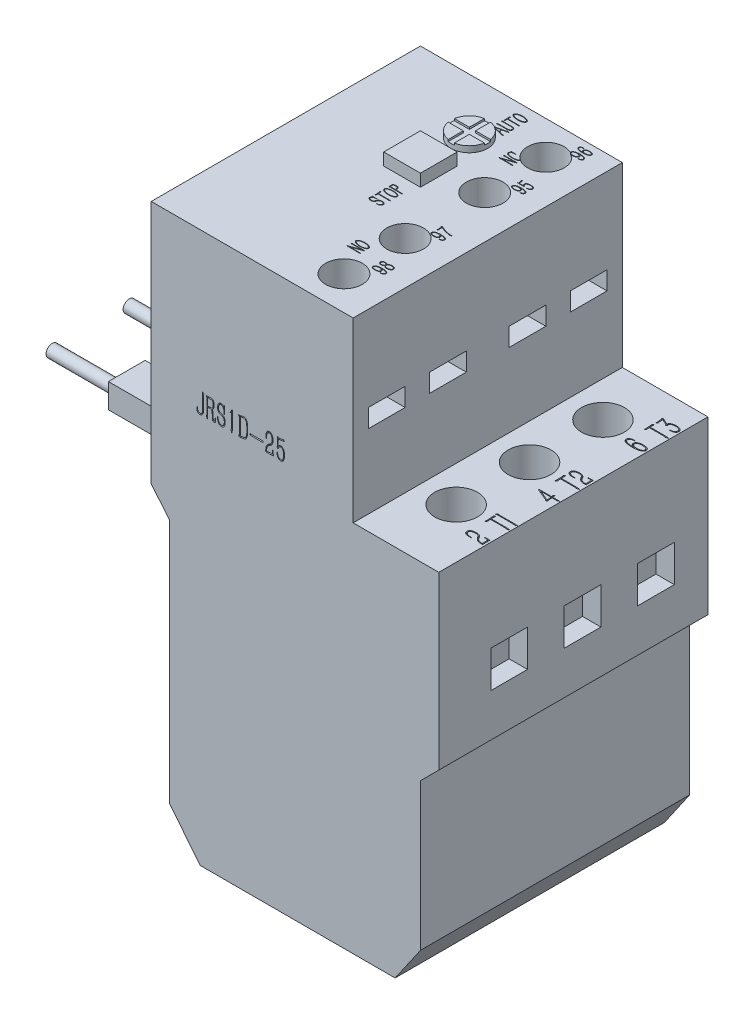
SolidWorks part; units mm, degrees
ref_plane "前视基准面" through (0, 0, 0) normal (0, 0, 1) x (1, 0, 0)
ref_plane "上视基准面" through (0, 0, 0) normal (0, 1, 0) x (1, 0, 0)
ref_plane "右视基准面" through (0, 0, 0) normal (1, 0, 0) x (0, 0, -1)
sketch "草图1" plane through (0, 0, 0) normal (0, 1, 0) x (1, 0, 0)
  line L1 (-23.5, 22) -> (23.5, 22)
  line L2 (-23.5, 22) -> (-23.5, -22)
  line L3 (-23.5, -22) -> (23.5, -22)
  line L4 (23.5, 22) -> (23.5, -22)
  line L5 (-23.5, 22) -> (23.5, -22) construction
  line L6 (-23.5, -22) -> (23.5, 22) construction
  point P0 (0, 0)
  dimension "D1" = 47
  dimension "D2" = 44
extrude "凸台-拉伸1" add sketch "草图1" along normal blind 90
fillet "圆角1" radius 5 1 edges at (23.5, 0, 0)
sketch "草图2" plane through (0, 0, 22) normal (0, 0, 1) x (1, 0, 0)
  line L0 (-23.5, 0) -> (-15.5, 0)
  line L2 (-23.5, 90) -> (-23.5, 0) construction
  line L3 (-23.5, 10) -> (-23.5, 0)
  line L4 (-23.5, 0) -> (18.5, 0) construction
  line L5 (-15.5, 0) -> (-23.5, 10)
  dimension "D1" = 10
  dimension "D2" = 8
extrude "切除-拉伸1" cut sketch "草图2" against normal blind 53
sketch "草图3" plane through (23.5, 0, 0) normal (1, 0, 0) x (0, 0, -1)
sketch "草图5" plane through (0, 0, 22) normal (0, 0, 1) x (1, 0, 0)
  line L0 (23.5, 61) -> (9.5, 61)
  line L1 (23.5, 90) -> (23.5, 5) construction
  line L2 (9.5, 61) -> (9.5, 90)
  line L3 (-23.5, 90) -> (23.5, 90) construction
  line L4 (9.5, 90) -> (23.5, 90)
  line L5 (23.5, 90) -> (23.5, 61)
  line L6 (-15.5, 0) -> (18.5, 0) construction
  dimension "D1" = 14
  dimension "D2" = 61
extrude "切除-拉伸3" cut sketch "草图5" against normal blind 53
sketch "草图6" plane through (-23.5, 0, 0) normal (-1, 0, 0) x (0, 0, 1)
  line L0 (8.4, 60) -> (2.4, 60)
  line L2 (22, 90) -> (22, 10) construction
  line L3 (21, 56) -> (15, 56)
  line L4 (21, 56) -> (21, 60)
  line L5 (21, 60) -> (15, 60)
  line L6 (15, 56) -> (15, 60)
  line L7 (8.4, 56) -> (8.4, 60)
  line L8 (2.4, 56) -> (2.4, 60)
  line L9 (8.4, 56) -> (2.4, 56)
  line L10 (-4.2, 60) -> (-10.2, 60)
  line L11 (-4.2, 56) -> (-4.2, 60)
  line L12 (-10.2, 56) -> (-10.2, 60)
  line L13 (-4.2, 56) -> (-10.2, 56)
  dimension "D2" = 4
  dimension "D1" = 3
  dimension "D3" = 1
  dimension "D4" = 6
extrude "凸台-拉伸2" add sketch "草图6" along normal blind 8
sketch "草图7" plane through (-31.5, 0, 0) normal (-1, 0, 0) x (0, 0, 1)
  circle A0 centre (19.1974, 58) radius 1
  circle A1 centre (6.5974, 58) radius 1
  circle A2 centre (-6.0026, 58) radius 1
  dimension "D1" = 2
  dimension "D2" = 3
extrude "凸台-拉伸3" add sketch "草图7" along normal blind 11
sketch "草图8" plane through (0, 0, 22) normal (0, 0, 1) x (1, 0, 0)
  line L0 (-23.5, 50) -> (-20.5, 46.3906)
  line L1 (-23.5, 90) -> (-23.5, 10) construction
  line L2 (-20.5, 46.3906) -> (-20.5, 5.4883)
  line L4 (-23.5, 50) -> (-23.5, 10)
  line L5 (-23.5, 10) -> (-20.5, 5.4883)
  dimension "D1" = 3
extrude "切除-拉伸4" cut sketch "草图8" against normal blind 64
sketch "草图9" plane through (0, 61, 0) normal (0, 1, 0) x (1, 0, 0)
  line L0 (23.5, 22) -> (18.5, 22) construction
  line L1 (9.5, 22) -> (23.5, 22) construction
  circle A0 centre (15.3377, 13) radius 3.5
  dimension "D1" = 7
  dimension "D2" = 9
extrude "切除-拉伸5" cut sketch "草图9" against normal blind 15
pattern_linear "阵列(线性)1" count 3 spacing 12 along (0, 0, 1) of "切除-拉伸5"
sketch "草图11" plane through (23.5, 0, 0) normal (1, 0, 0) x (0, 0, -1)
  line L0 (22, 61) -> (22, 5) construction
  line L1 (16.5, 46) -> (10.5, 46)
  line L2 (16.5, 46) -> (16.5, 40)
  line L3 (16.5, 40) -> (10.5, 40)
  line L4 (10.5, 46) -> (10.5, 40)
  line L5 (22, 61) -> (-22, 61) construction
  dimension "D1" = 5.5
  dimension "D2" = 15
  dimension "D3" = 6
  dimension "D4" = 6
extrude "切除-拉伸7" cut sketch "草图11" against normal blind 3
pattern_linear "阵列(线性)2" count 3 spacing 12 along (0, 0, 1) of "切除-拉伸7"
sketch "草图12" plane through (0, 0, 22) normal (0, 0, 1) x (1, 0, 0)
  line L0 (23.5, 33) -> (20.5186, 30.0186)
  line L1 (23.5, 61) -> (23.5, 5) construction
  line L2 (20.5186, 30.0186) -> (20.5186, 6.0037)
  line L3 (20.5186, 6.0037) -> (16.3593, 0)
  line L4 (-15.5, 0) -> (18.5, 0) construction
  line L5 (16.3593, 0) -> (23.5, 0)
  line L6 (23.5, 0) -> (23.5, 33)
extrude "切除-拉伸8" cut sketch "草图12" against normal blind 61
sketch "草图13" plane through (0, 90, 0) normal (0, 1, 0) x (1, 0, 0)
  line L0 (9.5, 22) -> (-23.5, 22) construction
  line L1 (9.5, 22) -> (9.5, -22) construction
  circle A0 centre (2.5, 16.5) radius 3
  dimension "D1" = 6
  dimension "D2" = 5.5
  dimension "D3" = 7
extrude "切除-拉伸9" cut sketch "草图13" against normal blind 10
pattern_linear "阵列(线性)3" count 2 spacing 10 along (0, 0, 1) of "切除-拉伸9"
mirror "镜向1" about plane through (0, 0, 0) normal (0, 0, 1) of "阵列(线性)3"
sketch "草图14" plane through (9.5, 0, 0) normal (1, 0, 0) x (0, 0, -1)
  line L0 (22, 90) -> (22, 61) construction
  line L1 (19.5, 73.0813) -> (13.5, 73.0813)
  line L2 (19.5, 73.0813) -> (19.5, 76.0813)
  line L3 (19.5, 76.0813) -> (13.5, 76.0813)
  line L4 (13.5, 73.0813) -> (13.5, 76.0813)
  dimension "D1" = 6
  dimension "D2" = 2.5
  dimension "D3" = 3
extrude "切除-拉伸10" cut sketch "草图14" against normal blind 3
pattern_linear "阵列(线性)4" count 2 spacing 10 along (0, 0, 1) of "切除-拉伸10"
mirror "镜向2" about plane through (0, 0, 0) normal (0, 0, 1) of "阵列(线性)4"
sketch "草图15" plane through (0, 90, 0) normal (0, 1, 0) x (1, 0, 0)
  line L1 (-9.5, 8) -> (-3.5, 8)
  line L2 (-9.5, 8) -> (-9.5, 2)
  line L3 (-9.5, 2) -> (-3.5, 2)
  line L4 (-3.5, 8) -> (-3.5, 2)
  line L5 (9.5, 22) -> (-23.5, 22) construction
  line L6 (-23.5, 4.2) -> (-23.5, 10.2) construction
  point P6 (-23.5, 7.2)
  dimension "D1" = 20
  dimension "D2" = 6
  dimension "D3" = 6
  dimension "D4" = 20
extrude "凸台-拉伸4" add sketch "草图15" along normal blind 2
sketch "草图16" plane through (0, 90, 0) normal (0, 1, 0) x (1, 0, 0)
  line L0 (-3.5, 8) -> (-9.5, 8) construction
  circle A0 centre (-6.5, 13) radius 3
  point P2 (-6.5, 8)
  dimension "D1" = 5
  dimension "D2" = 6
extrude "凸台-拉伸5" add sketch "草图16" along normal blind 1
sketch "草图17" plane through (0, 91, 0) normal (0, 1, 0) x (1, 0, 0)
  line L0 (-6, 12.5) -> (-6, 10)
  line L1 (-7, 16) -> (-7, 13.5)
  line L2 (-6, 12.5) -> (-3.5, 12.5)
  line L3 (-9.5, 12.5) -> (-7, 12.5)
  line L4 (-6, 16) -> (-6, 13.5)
  line L5 (-9.5, 13.5) -> (-7, 13.5)
  line L6 (-7, 16) -> (-6, 16)
  line L7 (-6, 16) -> (-5.9956, 16.1226)
  line L8 (-3.5, 13.5) -> (-3.5, 12.5)
  line L9 (-7, 10) -> (-6, 10)
  line L10 (-9.5, 12.5) -> (-9.5, 13.5)
  line L11 (-7, 12.5) -> (-7, 10)
  line L12 (-6, 13.5) -> (-3.5, 13.5)
  circle M1 centre (-6.5, 13) radius 3
extrude "切除-拉伸11" cut sketch "草图17" against normal blind 0.3 contours L12 L4 L1 L5 L3 L11 L0 L2 M1 region at (-6.5, 91, -13)
sketch "草图18" plane through (6.5, 0, 0) normal (1, 0, 0) x (0, 0, -1)
  point P0 (-16.5, 74.5813)
  point P1 (-6.5, 74.5813)
  point P2 (6.5, 74.5813)
  point P3 (16.5, 74.5813)
sketch "草图19" plane through (20.5, 0, 0) normal (1, 0, 0) x (0, 0, -1)
  point P0 (-10.5, 43)
  point P1 (1.5, 43)
  point P2 (13.5, 43)
sketch "草图20" plane through (0, 90, 0) normal (0, 1, 0) x (1, 0, 0)
  text T0 "\r\n\r\n\r\n            \r\n               STOP             AUTO  \r\n        NO                   NC \r\n       98      97         95      96" font "汉仪长仿宋体" height in points 9
extrude "切除-拉伸12" cut sketch "草图20" against normal blind 0.3
sketch "草图21" plane through (0, 61, 0) normal (0, 1, 0) x (1, 0, 0)
  text T0 "    2 TI   4 T2    6 T3  " font "汉仪长仿宋体" height 3.5
extrude "切除-拉伸13" cut sketch "草图21" against normal blind 0.3
sketch "草图22" plane through (0, 0, 22) normal (0, 0, 1) x (1, 0, 0)
  text T0 "\r\n\r\n    \r\n\r\n    JRS1D-25"
extrude "切除-拉伸14" cut sketch "草图22" against normal blind 0.3
sketch "0_0_Point" plane through (20.5, 0, 0) normal (1, 0, 0) x (0, 0, -1)
  point P0 (-10.5, 43)
other "0_0" parameters "直径"=2, "端头长度"=2
ref_axis "基准轴1" through (30.5, 43, 10.5) along (-1, 0, 0)
sketch "1_0_Point" plane through (20.5, 0, 0) normal (1, 0, 0) x (0, 0, -1)
  point P0 (1.5, 43)
other "1_0" parameters "直径"=2, "端头长度"=2
ref_axis "基准轴2" through (30.5, 43, -1.5) along (-1, 0, 0)
sketch "2_0_Point" plane through (20.5, 0, 0) normal (1, 0, 0) x (0, 0, -1)
  point P0 (13.5, 43)
other "2_0" parameters "直径"=2, "端头长度"=2
ref_axis "基准轴3" through (30.5, 43, -13.5) along (-1, 0, 0)
sketch "3_0_Point" plane through (6.5, 0, 0) normal (1, 0, 0) x (0, 0, -1)
  point P0 (-16.5, 74.5813)
other "3_0" parameters "直径"=2, "端头长度"=2
ref_axis "基准轴4" through (16.5, 74.5813, 16.5) along (-1, 0, 0)
sketch "3_1_Point" plane through (6.5, 0, 0) normal (1, 0, 0) x (0, 0, -1)
  point P0 (-6.5, 74.5813)
other "3_1" parameters "直径"=2, "端头长度"=2
ref_axis "基准轴5" through (16.5, 74.5813, 6.5) along (-1, 0, 0)
sketch "4_0_Point" plane through (6.5, 0, 0) normal (1, 0, 0) x (0, 0, -1)
  point P0 (6.5, 74.5813)
other "4_0" parameters "直径"=2, "端头长度"=2
ref_axis "基准轴6" through (16.5, 74.5813, -6.5) along (-1, 0, 0)
sketch "4_1_Point" plane through (6.5, 0, 0) normal (1, 0, 0) x (0, 0, -1)
  point P0 (16.5, 74.5813)
other "4_1" parameters "直径"=2, "端头长度"=2
ref_axis "基准轴7" through (16.5, 74.5813, -16.5) along (-1, 0, 0)
